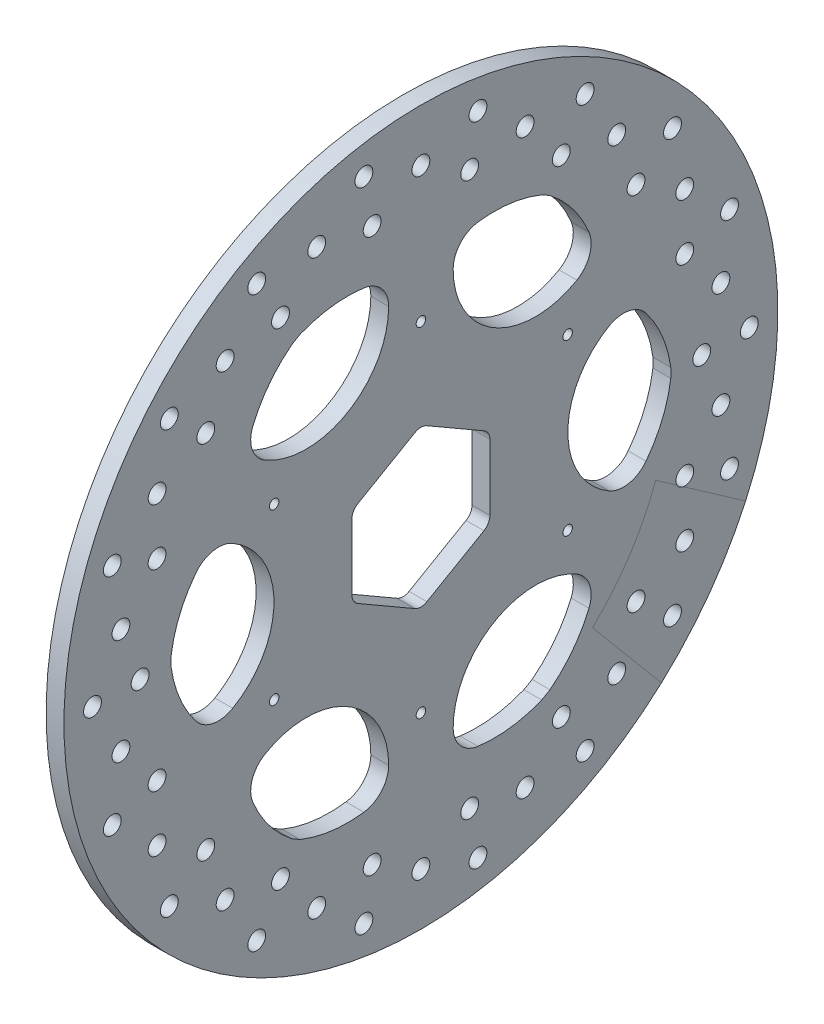
SolidWorks part; units mm, degrees
material "Gray Cast Iron (w/YS)"
ref_plane "X-Y Datum" through (0, 0, 0) normal (0, 0, 1) x (1, 0, 0)
ref_plane "X-Z Datum" through (0, 0, 0) normal (0, 1, 0) x (1, 0, 0)
ref_plane "Y-Z Datum" through (0, 0, 0) normal (1, 0, 0) x (0, 0, -1)
sketch "Sketch1" plane through (0, 0, 0) normal (1, 0, 0) x (0, 0, -1)
  circle A0 centre (0, 0) radius 95.25
  circle A1 centre (0, 0) radius 66.675
  dimension "D1" = 190.5
  dimension "D2" = 133.35
extrude "Main Rotor" add sketch "Sketch1" along normal blind 4.7625
sketch "Sketch2" plane through (4.7625, 0, 0) normal (1, 0, 0) x (0, 0, -1)
  line L0 (0, 0) -> (-50000, 0) construction
  line L1 (0, 0) -> (-93.8029, 16.54) construction
  line L4 (-82.3453, 29.9712) -> (-70.4112, 25.6276) construction
  circle A2 centre (0, 0) radius 95.25 construction
  circle A72 centre (-80.0452, 14.1141) radius 2.3813
  circle A73 centre (0, 0) radius 66.675 construction
  circle A74 centre (-82.3453, 29.9712) radius 2.3812
  circle A75 centre (-70.4112, 25.6276) radius 2.3813
  circle A76 centre (0, 0) radius 95.25 construction
  circle A77 centre (-70.3905, 40.64) radius 2.3812
  circle A78 centre (-67.1285, 56.3275) radius 2.3813
  circle A79 centre (0, 0) radius 66.675 construction
  circle A80 centre (-57.3997, 48.1641) radius 2.3813
  circle A81 centre (-52.2458, 62.2641) radius 2.3813
  circle A82 centre (-87.63, 0) radius 2.3813
  circle A83 centre (-43.815, 75.8898) radius 2.3812
  circle A84 centre (-37.465, 64.8913) radius 2.3813
  circle A85 centre (-74.93, 0) radius 2.3813
  circle A86 centre (-27.7994, 76.3782) radius 2.3812
  circle A87 centre (-15.2168, 86.2987) radius 2.3813
  circle A88 centre (-13.0115, 73.7916) radius 2.3813
  circle A89 centre (0, 81.28) radius 2.3813
  circle A90 centre (15.2168, 86.2987) radius 2.3813
  circle A91 centre (13.0115, 73.7916) radius 2.3813
  circle A92 centre (27.7994, 76.3782) radius 2.3813
  circle A93 centre (43.815, 75.8898) radius 2.3813
  circle A94 centre (37.465, 64.8913) radius 2.3813
  circle A95 centre (52.2458, 62.2641) radius 2.3813
  circle A96 centre (67.1285, 56.3275) radius 2.3813
  circle A97 centre (57.3997, 48.1641) radius 2.3813
  circle A98 centre (70.3905, 40.64) radius 2.3812
  circle A99 centre (82.3453, 29.9712) radius 2.3813
  circle A100 centre (70.4112, 25.6276) radius 2.3813
  circle A101 centre (80.0452, 14.1141) radius 2.3813
  circle A102 centre (87.63, 0) radius 2.3813
  circle A103 centre (74.93, 0) radius 2.3813
  circle A104 centre (80.0452, -14.1141) radius 2.3813
  circle A105 centre (82.3453, -29.9712) radius 2.3812
  circle A106 centre (70.4112, -25.6276) radius 2.3812
  circle A107 centre (70.3905, -40.64) radius 2.3813
  circle A108 centre (67.1285, -56.3275) radius 2.3812
  circle A109 centre (57.3997, -48.1641) radius 2.3813
  circle A110 centre (52.2458, -62.2641) radius 2.3812
  circle A111 centre (43.815, -75.8898) radius 2.3813
  circle A112 centre (37.465, -64.8913) radius 2.3813
  circle A113 centre (27.7994, -76.3782) radius 2.3813
  circle A114 centre (15.2168, -86.2987) radius 2.3813
  circle A115 centre (13.0115, -73.7916) radius 2.3812
  circle A116 centre (0, -81.28) radius 2.3812
  circle A117 centre (-15.2168, -86.2987) radius 2.3813
  circle A118 centre (-13.0115, -73.7916) radius 2.3813
  circle A119 centre (-27.7994, -76.3782) radius 2.3812
  circle A120 centre (-43.815, -75.8898) radius 2.3813
  circle A121 centre (-37.465, -64.8913) radius 2.3813
  circle A122 centre (-52.2458, -62.2641) radius 2.3813
  circle A123 centre (-67.1285, -56.3275) radius 2.3813
  circle A124 centre (-57.3997, -48.1641) radius 2.3813
  circle A125 centre (-70.3905, -40.64) radius 2.3813
  circle A126 centre (-82.3453, -29.9712) radius 2.3813
  circle A127 centre (-70.4112, -25.6276) radius 2.3813
  circle A128 centre (-80.0452, -14.1141) radius 2.3813
  point P109 (0, 0)
  dimension "D1" = 4.7625
  dimension "D2" = 12.7
  dimension "D3" = 10
  dimension "D5" = 81.28
  dimension "D4" = 87.63
  dimension "D6" = 18
extrude "Cut Slots" cut sketch "Sketch2" against normal through all
sketch "Sketch3" plane through (4.7625, 0, 0) normal (1, 0, 0) x (0, 0, -1)
  line L0 (0, 0) -> (-43301.2702, 25000) construction
  line L1 (0, 21.2491) -> (-18.4023, 10.6246)
  line L2 (-18.4023, 10.6246) -> (-18.4023, -10.6246)
  line L3 (-18.4023, -10.6246) -> (0, -21.2491)
  line L4 (0, -21.2491) -> (18.4023, -10.6246)
  line L5 (18.4023, -10.6246) -> (18.4023, 10.6246)
  line L6 (18.4023, 10.6246) -> (0, 21.2491)
  line L7 (0, 0) -> (43301.2702, 25000) construction
  line L8 (0, 0) -> (0, 50000) construction
  line L12 (9.525, -59.2994) -> (-9.525, -59.2994) construction
  line L17 (-30.6007, -53.002) -> (24969.3838, 43248.2414) construction
  line L18 (-60.783, 0) -> (49939.217, 0) construction
  line L19 (0, 0) -> (-25000, 43301.2702) construction
  arc A0 (8.6043, -53.0208) -> (15.2264, -60.5686) centre (16.2243, -53.0143) ccw
  circle A1 centre (0, 0) radius 66.675 construction
  arc A7 (-15.2264, -60.5686) -> (-32.2316, -58.3668) centre (-19.5921, -27.5182) cw
  arc A10 (15.2264, -60.5686) -> (32.2316, -58.3668) centre (19.5921, -27.5182) ccw
  arc A19 (-19.6024, -33.9524) -> (-8.6043, -53.0208) centre (-30.6006, -53.0019) cw
  arc A25 (41.6152, -33.9619) -> (44.8408, -43.4707) centre (37.7996, -40.5577) cw
  arc A26 (34.4313, -57.0968) -> (66.6629, -1.27) centre (0, 0) ccw
  arc A27 (50.2195, -19.0589) -> (60.0672, -17.0979) centre (54.0238, -12.4565) ccw
  arc A28 (19.6024, -33.9524) -> (8.6043, -53.0208) centre (30.6006, -53.0019) ccw
  arc A29 (60.0672, 17.0979) -> (50.2195, 19.0589) centre (54.0238, 12.4565) ccw
  arc A30 (-44.8408, -43.4707) -> (-34.4313, -57.0968) centre (-14.0354, -30.7264) ccw
  arc A31 (-19.6024, -33.9524) -> (-41.6152, -33.9619) centre (-30.6006, -53.0019) ccw
  arc A32 (-39.2049, 0) -> (-50.2195, -19.0589) centre (-61.2013, 0) cw
  arc A33 (-60.0672, -17.0979) -> (-66.6629, -1.27) centre (-33.6275, 3.2082) cw
  arc A34 (-60.0672, 17.0979) -> (-66.6629, 1.27) centre (-33.6275, -3.2082) ccw
  arc A35 (44.8408, 43.4707) -> (41.6152, 33.9619) centre (37.7996, 40.5577) cw
  arc A36 (-32.2316, -58.3668) -> (32.2316, -58.3668) centre (0, 0) ccw
  arc A37 (15.2264, 60.5686) -> (8.6043, 53.0208) centre (16.2243, 53.0143) ccw
  arc A38 (-8.6043, 53.0208) -> (-15.2264, 60.5686) centre (-16.2243, 53.0143) ccw
  arc A39 (-44.8408, 43.4707) -> (-41.6152, 33.9619) centre (-37.7996, 40.5577) ccw
  arc A40 (-50.2195, 19.0589) -> (-60.0672, 17.0979) centre (-54.0238, 12.4565) ccw
  arc A41 (-50.2195, -19.0589) -> (-60.0672, -17.0979) centre (-54.0238, -12.4565) cw
  arc A42 (-8.6043, -53.0208) -> (-15.2264, -60.5686) centre (-16.2243, -53.0143) cw
  arc A43 (-41.6152, -33.9619) -> (-44.8408, -43.4707) centre (-37.7996, -40.5577) ccw
  arc A44 (-39.2049, 0) -> (-50.2195, 19.0589) centre (-61.2013, 0) ccw
  arc A45 (-19.6025, 33.9524) -> (-41.6152, 33.9619) centre (-30.6007, 53.0019) cw
  arc A46 (-44.8408, 43.4707) -> (-34.4313, 57.0968) centre (-14.0354, 30.7264) cw
  arc A47 (-15.2264, 60.5686) -> (-32.2316, 58.3668) centre (-19.5921, 27.5182) ccw
  arc A48 (-19.6025, 33.9524) -> (-8.6043, 53.0208) centre (-30.6007, 53.0019) ccw
  arc A49 (19.6024, 33.9524) -> (8.6043, 53.0208) centre (30.6006, 53.0019) cw
  arc A50 (15.2264, 60.5686) -> (32.2316, 58.3668) centre (19.5921, 27.5182) cw
  arc A51 (44.8408, 43.4707) -> (34.4313, 57.0968) centre (14.0354, 30.7264) ccw
  arc A52 (19.6024, 33.9524) -> (41.6152, 33.9619) centre (30.6006, 53.0019) ccw
  arc A53 (39.2049, 0) -> (50.2195, 19.0589) centre (61.2013, 0) cw
  arc A54 (60.0672, 17.0979) -> (66.6629, 1.27) centre (33.6275, -3.2082) cw
  arc A55 (60.0672, -17.0979) -> (66.6629, -1.27) centre (33.6275, 3.2082) ccw
  arc A56 (39.2049, 0) -> (50.2195, -19.0589) centre (61.2013, 0) ccw
  arc A57 (19.6024, -33.9524) -> (41.6152, -33.9619) centre (30.6007, -53.0019) cw
  arc A58 (44.8408, -43.4707) -> (34.4313, -57.0968) centre (14.0354, -30.7264) cw
  arc A60 (-66.6629, -1.27) -> (-34.4313, -57.0968) centre (0, 0) ccw
  arc A62 (-34.4313, 57.0968) -> (-66.6629, 1.27) centre (0, 0) ccw
  arc A64 (32.2316, 58.3668) -> (-32.2316, 58.3668) centre (0, 0) ccw
  arc A66 (66.6629, 1.27) -> (34.4313, 57.0968) centre (0, 0) ccw
  point P34 (0, -59.2994)
  point P35 (-9.2012, 15.9369)
  point P124 (0, 0)
  dimension "D2" = 42.799
  dimension "D4" = 7.62
  dimension "D7" = 1.27
  dimension "D8" = 33.3375
  dimension "D9" = 21.9964
  dimension "D1" = 36.8046
  dimension "D3" = 6
  dimension "D6" = 19.05
extrude "Boss-Extrude2" add sketch "Sketch3" against normal up to surface (4.7625 mm away) up to face at (0, 0, 85.2488)
fillet "Fillet1" radius 3.175 6 edges at (2.3813, 10.6246, -18.4023) (2.3813, -10.6246, -18.4023) (2.3813, -21.2491, 0) (2.3813, -10.6246, 18.4023) (2.3813, 10.6246, 18.4023) (2.3813, 21.2491, 0)
sketch "Sketch4" plane through (0, 0, 0) normal (-1, 0, 0) x (0, 0, 1)
  circle A0 centre (0, 45.212) radius 1.27
  circle A1 centre (39.1547, 22.606) radius 1.27
  circle A2 centre (39.1547, -22.606) radius 1.27
  circle A3 centre (0, -45.212) radius 1.27
  circle A4 centre (-39.1547, -22.606) radius 1.27
  circle A5 centre (-39.1547, 22.606) radius 1.27
  point P16 (0, 0)
  dimension "D1" = 45.212
  dimension "D2" = 2.54
  dimension "D3" = 6
extrude "Cut-Extrude2" cut sketch "Sketch4" against normal through all
sketch "Sketch5" plane through (4.7625, 0, 0) normal (1, 0, 0) x (0, 0, -1)
  line L0 (0, 0) -> (-50000, 0) construction
  line L1 (0, 0) -> (-46984.631, 17101.0072) construction
  line L2 (62.654, -22.8042) -> (86.6311, -39.5931)
  line L3 (45.7933, -48.4616) -> (64.1833, -70.378)
  circle A0 centre (0, 0) radius 95.25 construction
  circle A1 centre (0, 0) radius 66.675 construction
  arc A2 (64.1833, -70.378) -> (86.6311, -39.5931) centre (0, 0) ccw
  arc A3 (45.7933, -48.4616) -> (62.654, -22.8042) centre (0, 0) ccw
  dimension "D1" = 20
  dimension "D2" = 15
  dimension "D3" = 15
  dimension "D4" = 38.1
split line "Split Line1"
ref_axis "Axis1" through (5.0006, 0, 0) along (-1, 0, 0)
